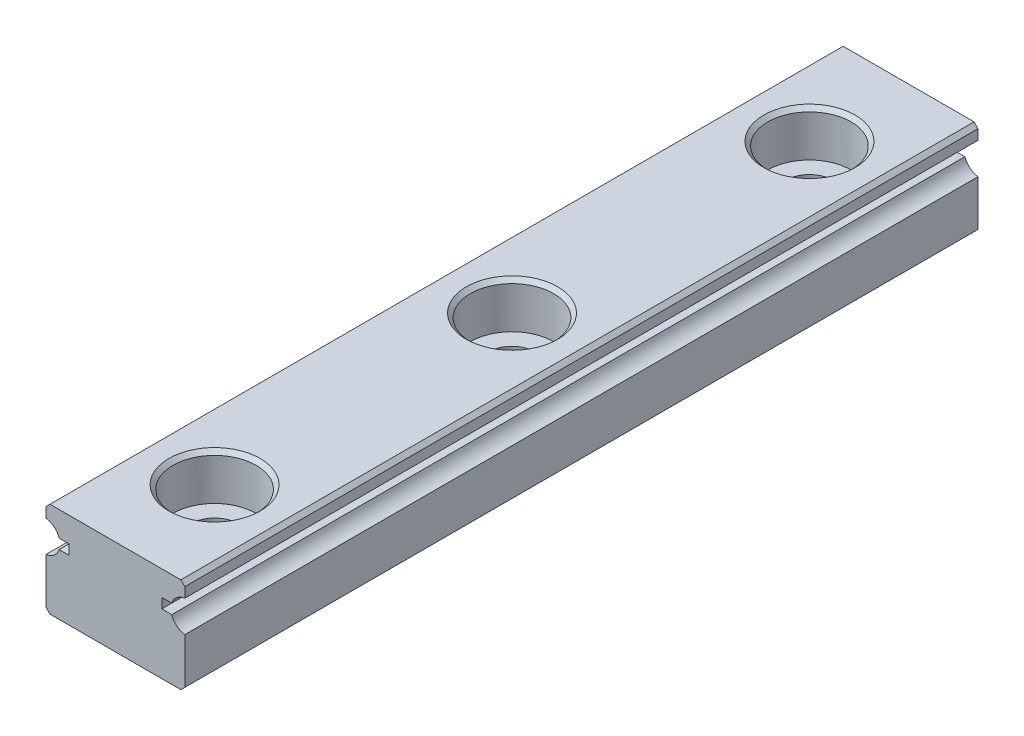
SolidWorks part; units mm, degrees
ref_plane "Спереди" through (0, 0, 0) normal (0, 0, 1) x (1, 0, 0)
ref_plane "Сверху" through (0, 0, 0) normal (0, 1, 0) x (1, 0, 0)
ref_plane "Справа" through (0, 0, 0) normal (1, 0, 0) x (0, 0, -1)
sketch "Sketch1" plane through (0, 0, 0) normal (0, 0, 1) x (1, 0, 0)
  line L0 (0, 0) -> (0, 4.3706) construction
  line L1 (-3.3, -2.4) -> (3.3, -2.4)
  line L2 (-3.5, -2.2) -> (-3.5, 0.1063)
  line L3 (-3.3, 2.4) -> (3.3, 2.4)
  line L4 (3.5, -2.2) -> (3.5, 0.1063)
  line L5 (-3.5, -2.4) -> (3.5, 2.4) construction
  line L6 (-3.5, 2.4) -> (3.5, -2.4) construction
  line L7 (-3.5, 1.6937) -> (-3.5, 2.2)
  line L8 (3.5, 1.6937) -> (3.5, 2.2)
  line L9 (-3.5, -2.2) -> (-3.3, -2.4)
  line L10 (3.3, -2.4) -> (3.5, -2.2)
  line L11 (3.3, 2.4) -> (3.5, 2.2)
  line L12 (-3.5, 2.2) -> (-3.3, 2.4)
  line L13 (2.8401, 0.65) -> (2.3401, 0.65)
  line L14 (-2.8401, 0.65) -> (-2.3401, 0.65)
  line L15 (2.3401, 0.65) -> (2.3401, 1.15)
  line L16 (-2.8401, 1.15) -> (-2.3401, 1.15)
  line L17 (-2.3401, 0.65) -> (-2.3401, 1.15)
  line L18 (2.8401, 1.15) -> (2.3401, 1.15)
  arc A0 (-3.5, 1.6937) -> (-2.8401, 1.15) centre (-3.6, 0.9) cw
  arc A1 (3.5, 1.6937) -> (2.8401, 1.15) centre (3.6, 0.9) ccw
  arc A2 (-2.8401, 0.65) -> (-3.5, 0.1063) centre (-3.6, 0.9) cw
  arc A3 (2.8401, 0.65) -> (3.5, 0.1063) centre (3.6, 0.9) ccw
  point P0 (0, 0)
  dimension "D4" = 0.8
  dimension "D5" = 0.1
  dimension "D1" = 7
  dimension "D2" = 4.8
  dimension "D3" = 1.5
  dimension "D6" = 0.5
  dimension "D7" = 0.5
extrude "Extrude1" add sketch "Sketch1" along normal blind 40
sketch "Sketch2" plane through (0, 2.4, 0) normal (0, 1, 0) x (1, 0, 0)
  line L0 (0, 0) -> (0, -5) construction
  circle A0 centre (0, -5) radius 1.2
  circle A1 centre (0, -5) radius 2.1
  dimension "D1" = 2.4
  dimension "D2" = 4.2
  dimension "D3" = 5
extrude "Extrude2" cut sketch "Sketch2" against normal up to next contours A0 region at (0, 2.4, 5)
extrude "Extrude4" cut sketch "Sketch" against normal blind 2.3
sketch "Sketch" plane through (0, 2.4, 0) normal (0, 1, 0) x (1, 0, 0) same geometry as "Sketch2"
chamfer "Chamfer1" distance 0.2 angle 45 2 edges at (0, -2.4, 6.2) (0, 2.4, 7.1)
pattern_linear "LPattern1" count 3 spacing 15 along (0, 0, 1) of "Extrude4", "Chamfer1", "Extrude2"
